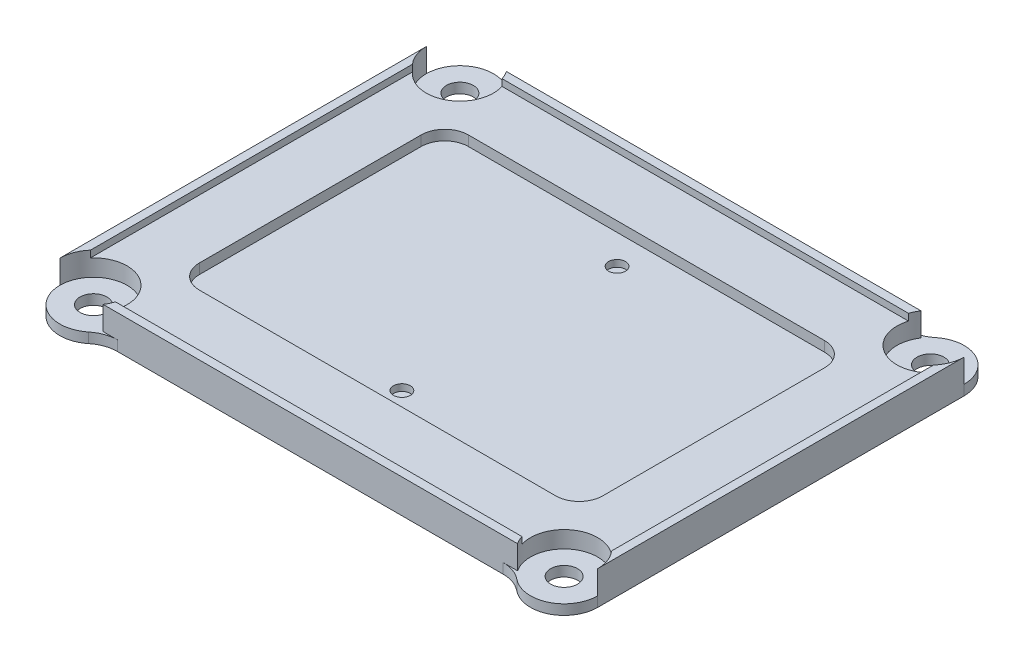
SolidWorks part; units mm, degrees
ref_plane "Front Plane" through (0, 0, 0) normal (0, 0, 1) x (1, 0, 0)
ref_plane "Top Plane" through (0, 0, 0) normal (0, 1, 0) x (1, 0, 0)
ref_plane "Right Plane" through (0, 0, 0) normal (1, 0, 0) x (0, 0, -1)
sketch "Sketch1" plane through (0, 0, 0) normal (0, 1, 0) x (1, 0, 0)
  line L0 (-70, 54.5) -> (66.8873, 54.5) construction
  line L1 (80, -64.5) -> (-80, -64.5)
  line L2 (80, -64.5) -> (80, 64.5)
  line L3 (80, 64.5) -> (-80, 64.5)
  line L4 (-80, -64.5) -> (-80, 64.5)
  line L5 (0, 64.5) -> (0, -64.5) construction
  line L6 (80, 0) -> (-80, 0) construction
  line L7 (53, -40) -> (-53, -40)
  line L8 (60, -33) -> (60, 33)
  line L9 (53, 40) -> (-53, 40)
  line L10 (-60, -33) -> (-60, 33)
  line L11 (0, 40) -> (0, -40) construction
  line L12 (60, 0) -> (-60, 0) construction
  line L13 (-70, 50.5) -> (-48.7993, 50.5) construction
  line L14 (-70, -50.5) -> (-35.916, -50.5) construction
  line L15 (-70, 50.5) -> (-70, -50.5) construction
  line L16 (-70, -54.5) -> (66.8873, -54.5) construction
  line L17 (-67.2741, 57.5) -> (-72.6458, 57.5)
  line L18 (77.5, -57.5) -> (-77.5, -57.5)
  line L19 (77.5, -57.5) -> (77.5, 57.5)
  line L20 (77.5, 57.5) -> (-62.5, 57.5)
  line L21 (-77.5, -57.5) -> (-77.5, 57.5)
  line L22 (0, 57.5) -> (0, -57.5) construction
  line L23 (77.5, 0) -> (-77.5, 0) construction
  line L24 (-77.5, 57.5) -> (-72.6458, 57.5)
  line L25 (-67.2741, 57.5) -> (-62.5, 57.5)
  line L26 (-61.6484, 60) -> (61.6484, 60)
  line L27 (-61.6484, -60) -> (61.6484, -60)
  arc A0 (-60, -33) -> (-53, -40) centre (-53, -33) ccw
  arc A1 (60, -33) -> (53, -40) centre (53, -33) cw
  arc A2 (60, 33) -> (53, 40) centre (53, 33) ccw
  arc A3 (-53, 40) -> (-60, 33) centre (-53, 33) ccw
  circle A4 centre (0, 31.25) radius 2.5
  circle A6 centre (-70, 54.5) radius 4
  circle A7 centre (-70, -54.5) radius 4
  circle A8 centre (70, -54.5) radius 4
  circle A9 centre (70, 54.5) radius 4
  circle A16 centre (-70, 54.5) radius 10
  circle A17 centre (70, 54.5) radius 10
  circle A18 centre (-70, -54.5) radius 10
  circle A19 centre (70, -54.5) radius 10
  circle A21 centre (0, -32.75) radius 2.5
  point P0 (0, 0)
  point P4 (0, 0)
  point P10 (-60, -40)
  point P16 (60, 40)
  point P19 (-60, 40)
  point P33 (-70, 0)
  point P34 (0, 0)
  point P39 (-70, 58.5)
  point P44 (70, 58.5)
  dimension "D5" = 7
  dimension "D6" = 5
  dimension "D8" = 2.5
  dimension "D9" = 8
  dimension "D14" = 5
  dimension "D1" = 129
  dimension "D2" = 160
  dimension "D3" = 120
  dimension "D4" = 80
  dimension "D7" = 8.75
  dimension "D10" = 101
  dimension "D11" = 70
  dimension "D12" = 155
  dimension "D13" = 115
  dimension "D15" = 7.25
extrude "Boss-Extrude1" add sketch "Sketch1" along normal blind 8 contours L1 L4 L3 L2
extrude "Cut-Extrude2" cut sketch "Sketch1<3>" along normal through all contours A6 | A9 | A8 | A7
sketch "Sketch1<3>" plane through (0, 0, 0) normal (0, 1, 0) x (1, 0, 0) same geometry as "Sketch1"
fillet "Fillet1" radius 10 4 edges at (80, 4, 64.5) (-80, 4, 64.5) (-80, 4, -64.5) (80, 4, -64.5)
extrude "Cut-Extrude4" cut sketch "Sketch1<11>" against normal blind 3 and the other way blind 1 from surface contours L9 A3 L10 A0 L7 A1 L8 A2 starting at face at (-70, 8, 58.5)
sketch "Sketch1<11>" plane through (0, 0, 0) normal (0, 1, 0) x (1, 0, 0) same geometry as "Sketch1"
extrude "Cut-Extrude9" cut sketch "Sketch1<13>" along normal through all contours A19 L27 A18 L1 | A17 L3 A16 L26 region at (0, 0, 62.2876) region at (0, 0, -62.2876)
sketch "Sketch1<13>" plane through (0, 0, 0) normal (0, 1, 0) x (1, 0, 0) same geometry as "Sketch1"
extrude "Cut-Extrude10" cut sketch "Sketch1<17>" against normal blind 5 from surface contours A16 | A18 | A19 | A17 | A4 | A21 starting at face at (0, 8, 0)
sketch "Sketch1<17>" plane through (0, 0, 0) normal (0, 1, 0) x (1, 0, 0) same geometry as "Sketch1"
extrude "Boss-Extrude4" add sketch "Sketch1<18>" along normal blind 10 contours A17 L26 A16 L20 | A18 L21 A16 L4 | A19 L2 A17 L19 | A19 L18 A18 L27 region at (78.7716, 0, 0) region at (0, 0, 58.754) region at (-78.7716, 0, 0) region at (0, 0, -58.754)
sketch "Sketch1<18>" plane through (0, 0, 0) normal (0, 1, 0) x (1, 0, 0) same geometry as "Sketch1"
fillet "Fillet2" radius 10 4 edges at (61.6484, 1.5, 60) (-61.6484, 1.5, 60) (61.6484, 1.5, -60) (-61.6484, 1.5, -60)
